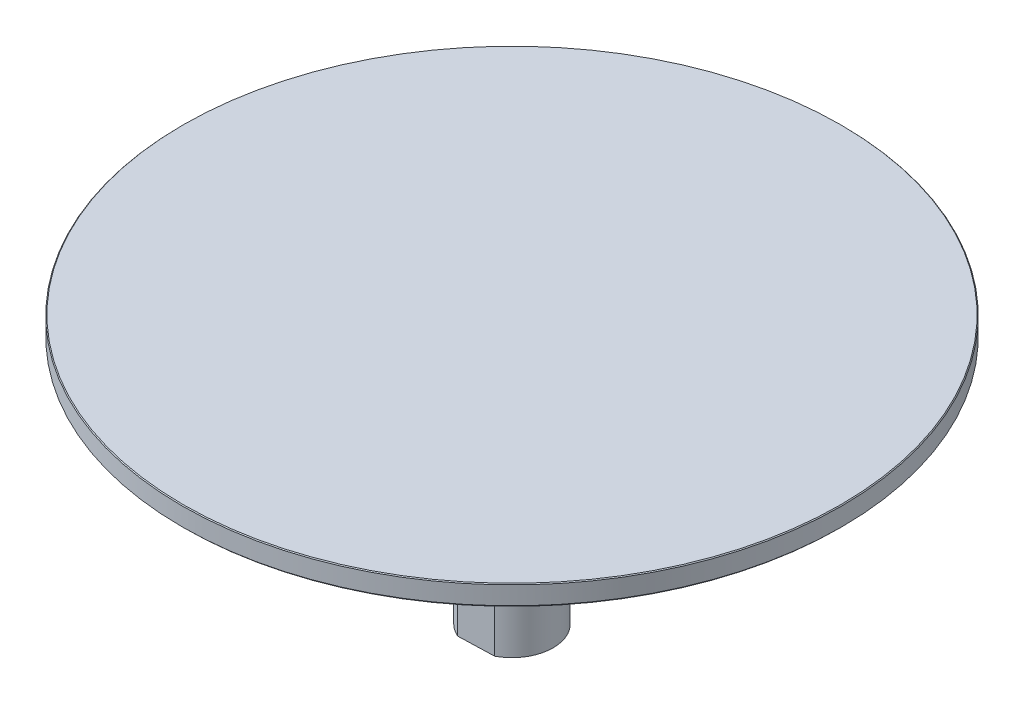
SolidWorks part; units mm, degrees
ref_plane "前视基准面" through (0, 0, 0) normal (0, 0, 1) x (1, 0, 0)
ref_plane "上视基准面" through (0, 0, 0) normal (0, 1, 0) x (1, 0, 0)
ref_plane "右视基准面" through (0, 0, 0) normal (1, 0, 0) x (0, 0, -1)
other "Configuration Table"
sketch "草图1" plane through (0, 0, 0) normal (0, 1, 0) x (1, 0, 0)
  circle A0 centre (0, 0) radius 80
  dimension "D1" = 160
extrude "凸台-拉伸1" add sketch "草图1" along normal blind 5
sketch "草图2" plane through (0, 0, 0) normal (0, -1, 0) x (-1, 0, 0)
  circle A0 centre (0, 0) radius 10
  dimension "D1" = 20
extrude "凸台-拉伸2" add sketch "草图2" along normal blind 60
chamfer "倒角1" distance 0.2 angle 45 1 edges at (0, 5, 80)
sketch "草图3" plane through (0, -60, 0) normal (0, -1, 0) x (-1, 0, 0)
  line L0 (4.0793, -9.1301) -> (-4.6343, -8.8613)
  arc A0 (-4.6343, -8.8613) -> (4.0793, -9.1301) centre (0, 0) ccw
  dimension "D1" = 20
  dimension "D2" = 9
extrude "切除-拉伸1" cut sketch "草图3" against normal up to surface (60 mm away) up to face at (0, 0, 10)
chamfer "倒角2" distance 0.4 angle 45 3 edges at (0, 0, 80) (0.2775, 0, 8.9957) (-0.3083, 0, -9.9952)
